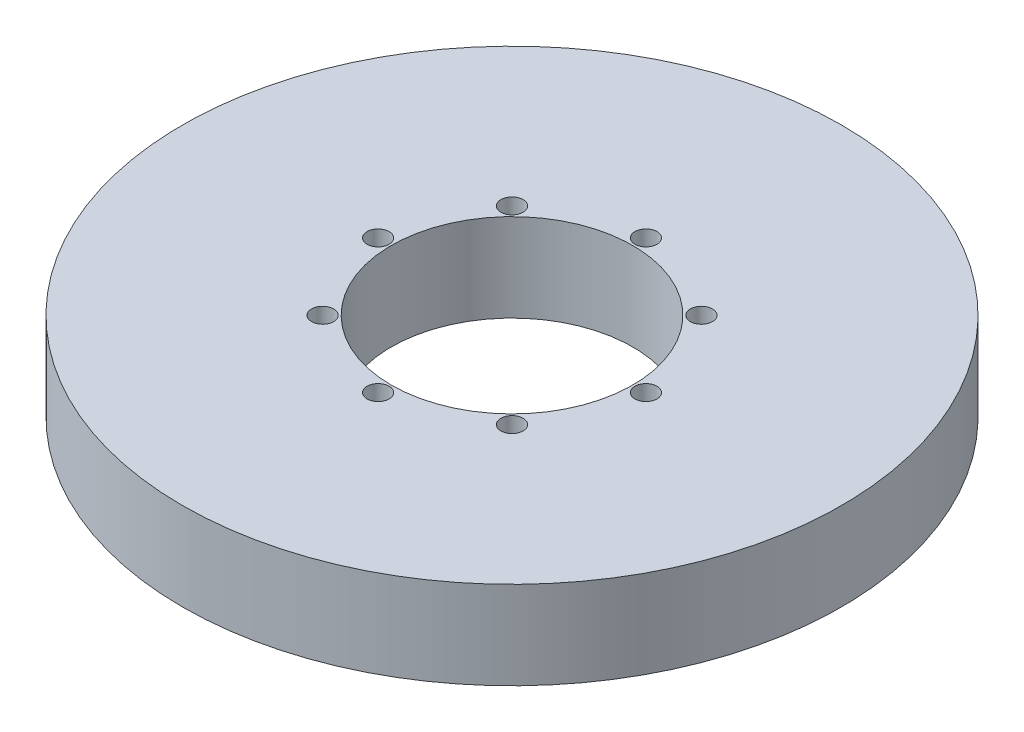
SolidWorks part; units mm, degrees
ref_plane "Front Plane" through (0, 0, 0) normal (0, 0, 1) x (1, 0, 0)
ref_plane "Top Plane" through (0, 0, 0) normal (0, 1, 0) x (1, 0, 0)
ref_plane "Right Plane" through (0, 0, 0) normal (1, 0, 0) x (0, 0, -1)
sketch "Sketch1" plane through (0, 0, 0) normal (0, 1, 0) x (1, 0, 0)
  circle A0 centre (0, 0) radius 75
  dimension "FLANGE_OD" = 150
extrude "Boss-Extrude1" add sketch "Sketch1" along normal blind 20
sketch "Sketch2" plane through (0, 0, 0) normal (0, 1, 0) x (1, 0, 0)
  circle A0 centre (0, 0) radius 27.5
  dimension "BORE_D" = 55
extrude "Cut-Extrude1" cut sketch "Sketch2" along normal through all
sketch "Sketch3" plane through (0, 20, 0) normal (0, 1, 0) x (1, 0, 0)
  circle A0 centre (0, 0) radius 30.4764 construction
  circle A1 centre (-30.4764, 0) radius 2.5131
  dimension "BOLT_D" = 5.0263
  dimension "BOLT_PCD" = 60.9529
extrude "Cut-Extrude2" cut sketch "Sketch3" against normal blind 19.9371
pattern_circular "CirPattern1" count 8 over 360 about axis through (0, 0, 0) along (0, 1, 0) of "Cut-Extrude2"
